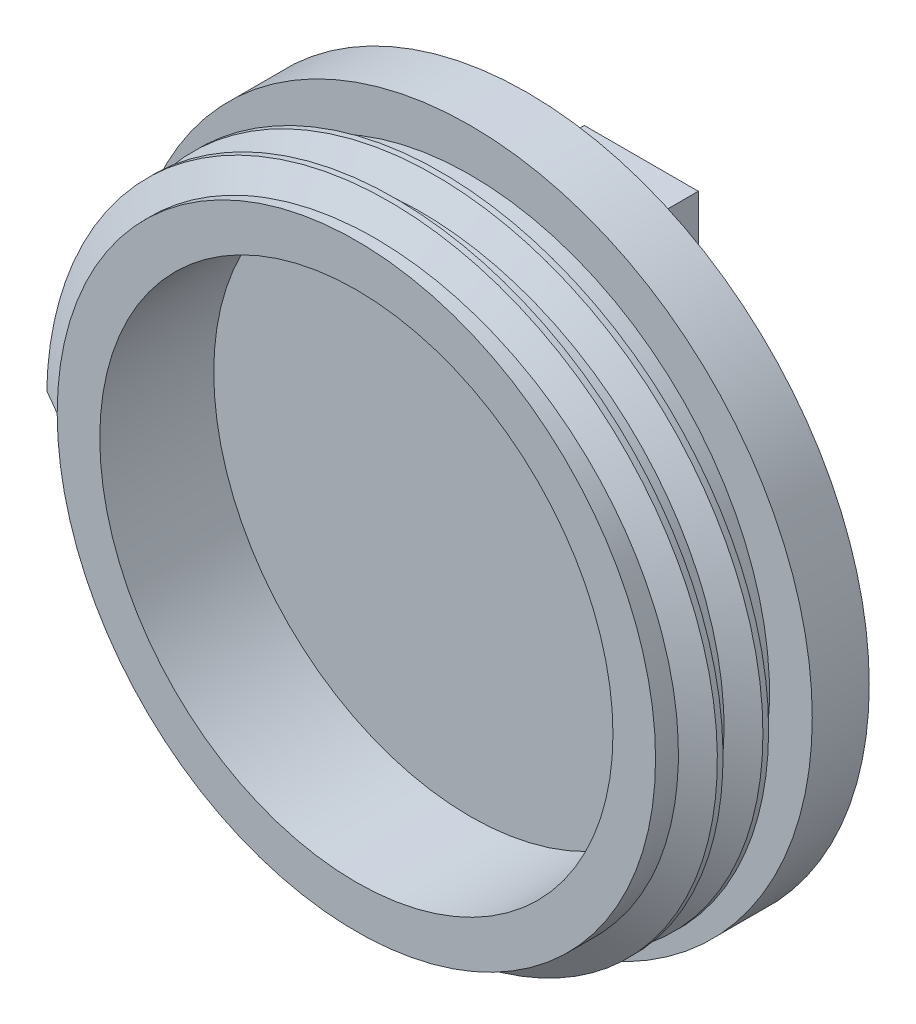
SolidWorks part; units mm, degrees
ref_plane "Plan de face" through (0, 0, 0) normal (0, 0, 1) x (1, 0, 0)
ref_plane "Plan de dessus" through (0, 0, 0) normal (0, 1, 0) x (1, 0, 0)
ref_plane "Plan de droite" through (0, 0, 0) normal (1, 0, 0) x (0, 0, -1)
sketch "Sketch1" plane through (0, 0, 0) normal (0, 0, 1) x (1, 0, 0)
  circle A0 centre (0, 0) radius 5.25
  dimension "D1" = 10.5
extrude "Boss-Extrude1" add sketch "Sketch1" along normal blind 2
thread "Thread1" pitch 0.8 method extrude profile "Thread Profile1" start angle 0, offset 0, length 1.5, pitch 0.8, diameter 10.5
ref_plane "Plane1" through (-5.25, 0, 2) normal (0, -1, 0) x (-1, 0, 0)
sketch "Thread Profile1" plane through (-5.25, 0, 2) normal (0, -1, 0) x (-1, 0, 0)
  line L0 (0, 0) -> (0, 0.8) construction
  line L1 (0, 0) -> (0.433, 0.25)
  line L2 (0.433, 0.25) -> (0.433, 0.35)
  line L3 (0.433, 0.35) -> (0, 0.6)
  line L4 (0.433, 0.3) -> (0, 0.3) construction
  line L11 (0, 0) -> (0, 0.6)
  point P2 (0, 0)
  dimension "Pitch" = 0.8
  dimension "Profile_Angle" = 60
  dimension "Profile_Land" = 0.1
  dimension "Profile_Height" = 0.433
sketch "Sketch4" plane through (0, 0, 0) normal (0, 0, -1) x (-1, 0, 0)
  circle A0 centre (0, 0) radius 6
  dimension "D1" = 12
extrude "Boss-Extrude2" add sketch "Sketch4" along normal blind 1
sketch "Sketch5" plane through (0, 0, 2) normal (0, 0, 1) x (1, 0, 0)
  circle A0 centre (0, 0) radius 4.5026
extrude "Cut-Extrude1" cut sketch "Sketch5" against normal blind 4
sketch "Sketch7" plane through (0, 0, -1) normal (0, 0, -1) x (-1, 0, 0)
  circle A0 centre (0, 0) radius 4.0311
  circle A1 centre (0, 0) radius 6 construction
  circle A2 centre (0, 0) radius 6
  dimension "D1" = 8.0622
extrude "Boss-Extrude3" add sketch "Sketch7" against normal blind 1
sketch "Sketch8" plane through (0, 0, -1) normal (0, 0, -1) x (-1, 0, 0)
  circle A1 centre (0, 0) radius 6
  circle A2 centre (0, 0) radius 6
  dimension "D1" = 0
extrude "Boss-Extrude4" add sketch "Sketch8" against normal up to surface (1 mm away) up to face at (-4.0311, 0, 0)
sketch "Sketch9" plane through (0, 0, -1) normal (0, 0, -1) x (-1, 0, 0)
  line L0 (0, 6) -> (0, -6) construction
  line L2 (-1, 4) -> (1, 4)
  line L3 (-1, 4) -> (-1, -4)
  line L4 (-1, -4) -> (1, -4)
  line L5 (1, 4) -> (1, -4)
  circle A0 centre (0, 0) radius 6 construction
  dimension "D1" = 4
  dimension "D2" = 4
  dimension "D3" = 1
  dimension "D4" = 1
extrude "Boss-Extrude5" add sketch "Sketch9" along normal blind 2
fillet "Fillet1" radius 1 4 edges at (0, -4, -1) (0, 4, -1) (1, 0, -1) (-1, 0, -1)
